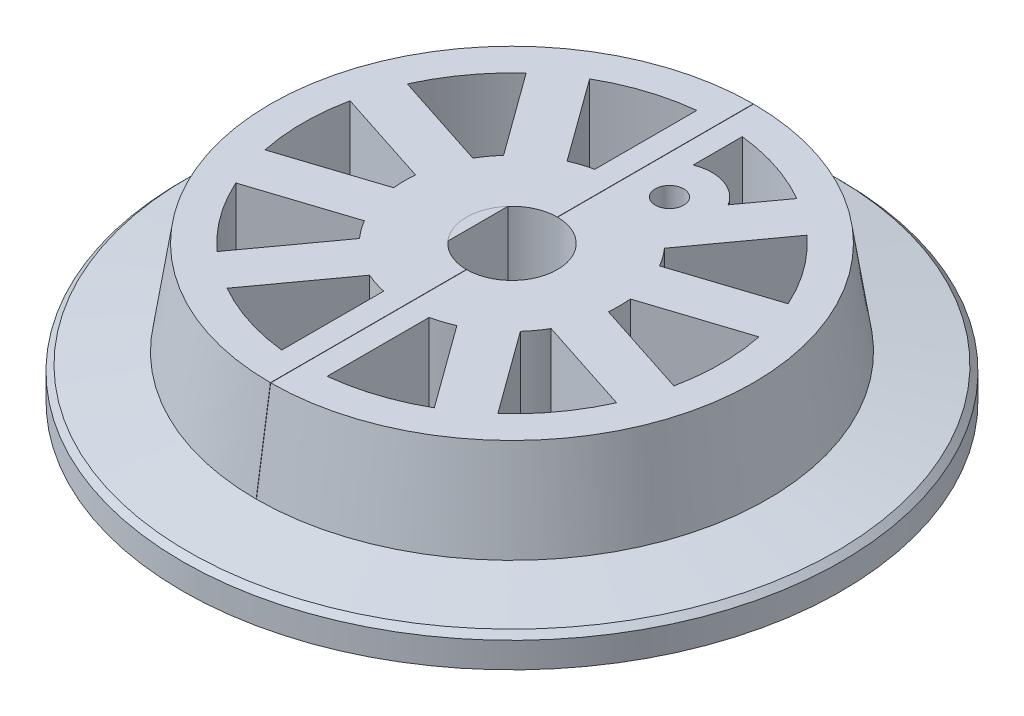
SolidWorks part; units mm, degrees
other "标注1"
sketch "草图3" plane through (-22.25, 4, -10) normal (-0.231, 0.6469, -0.7268) x (-0.9696, -0.2151, 0.1167)
ref_plane "前视基准面" through (0, 0, 0) normal (0, 0, 1) x (1, 0, 0)
ref_plane "上视基准面" through (0, 0, 0) normal (0, 1, 0) x (1, 0, 0)
ref_plane "右视基准面" through (0, 0, 0) normal (1, 0, 0) x (0, 0, -1)
other "Configuration Table"
sketch "草图4" plane through (0, 0, 0) normal (0, 1, 0) x (1, 0, 0)
  line L0 (-1.2, 1.0583) -> (-1.2, -1.0583)
  circle A0 centre (0, 0) radius 11.6
  circle A1 centre (0, 0) radius 1.6
  circle A2 centre (0, 0) radius 9
  dimension "D1" = 23.2
  dimension "D2" = 3.2
  dimension "D3" = 18
  dimension "D4" = 1.2
extrude "凸台-拉伸1" add sketch "草图4" along normal blind 1.1 contours A0 | A1
extrude "凸台-拉伸2" add sketch "草图4<3>" along normal blind 3.3 from offset 1.5 contours A2 | A1
sketch "草图4<3>" plane through (0, 0, 0) normal (0, 1, 0) x (1, 0, 0) same geometry as "草图4"
chamfer "倒角1" distance 0.2 angle 45 1 edges at (0, 1.1, 11.6)
loft "放样1" add section edge at (0, 1.5, 9) section edge at (0, 1.1, 11.4)
extrude "切除-拉伸2" cut sketch "草图4<4>" along normal through all contours A1
sketch "草图4<4>" plane through (0, 0, 0) normal (0, 1, 0) x (1, 0, 0) same geometry as "草图4"
chamfer "倒角2" distance 3.3 distance2 0.5 1 edges at (0, 4.8, 9) first distance on face at (0, 4.8, 9)
sketch "草图5" plane through (0, 4.8, 0) normal (0, 1, 0) x (1, 0, 0)
  line L0 (-0.8, 3.7148) -> (-0.8, 7.3063)
  line L1 (0, 3.8) -> (0, 7.35) construction
  line L2 (0.8, 7.3063) -> (0.8, 3.7148)
  circle A0 centre (0, 0) radius 3.8
  circle A1 centre (0, 0) radius 7.35
  dimension "D1" = 7.6
  dimension "D2" = 14.7
  dimension "D3" = 0.8
  dimension "D4" = 0.8
extrude "切除-拉伸4" cut sketch "草图5" against normal through all contours L0 A1 L2 A0 | A0 L1 A1 L0 | L1 A0 L2 A1 region at (-2.5179, 4.8, 3.1178) region at (-0.4008, 4.8, -5.5535) region at (0.4008, 4.8, -5.5535)
extrude "凸台-拉伸3" add sketch "草图5<4>" against normal up to surface (4.8 mm away) contours L1 A0 L2 A1 | A0 L1 A1 L0 region at (-0.4008, 4.8, -5.5535) region at (0.4008, 4.8, -5.5535) up to face at (0, 0, 7.35)
sketch "草图5<4>" plane through (0, 4.8, 0) normal (0, 1, 0) x (1, 0, 0) same geometry as "草图5"
pattern_circular "阵列(圆周)2" count 10 over 360 about axis through (0, 1.1, 0) along (0, -1, 0) of "凸台-拉伸3" reverse direction yes
sketch "草图6" plane through (0, 4.8, 0) normal (0, 1, 0) x (1, 0, 0)
  line L0 (0.8, 3.7148) -> (1.5363, 3.4756) construction
  line L1 (1.3597, 4.1846) -> (1.1682, 3.5952) construction
  circle A0 centre (1.3597, 4.1846) radius 0.5
  circle A1 centre (1.3597, 4.1846) radius 1.5
  dimension "D2" = 1
  dimension "D3" = 1
  dimension "D1" = 4.4
extrude "凸台-拉伸4" add sketch "草图6" against normal through all contours A1
extrude "切除-拉伸5" cut sketch "草图6<3>" against normal through all contours A0
sketch "草图6<3>" plane through (0, 4.8, 0) normal (0, 1, 0) x (1, 0, 0) same geometry as "草图6"
extrude "凸台-拉伸5" add sketch "草图4<6>" along normal up to surface (4.8 mm away) separate body contours L0 A1 region at (-1.3618, 0, 0) up to face at (1.3597, 4.8, -3.6846)
sketch "草图4<6>" plane through (0, 0, 0) normal (0, 1, 0) x (1, 0, 0) same geometry as "草图4"
sketch "草图7" plane through (0, 4.8, 0) normal (0, 1, 0) x (1, 0, 0)
  line L0 (-0.005, 11.4) -> (0.005, -11.4) construction
  line L1 (-0.005, 11.4) -> (0.005, 11.4)
  line L2 (-0.005, 11.4) -> (-0.005, -11.4)
  line L3 (-0.005, -11.4) -> (0.005, -11.4)
  line L4 (0.005, 11.4) -> (0.005, -11.4)
  circle A0 centre (0, 0) radius 11.4 construction
  point P4 (0, 0)
  dimension "D1" = 0.01
extrude "切除-拉伸6" cut sketch "草图7" against normal blind 3.3
